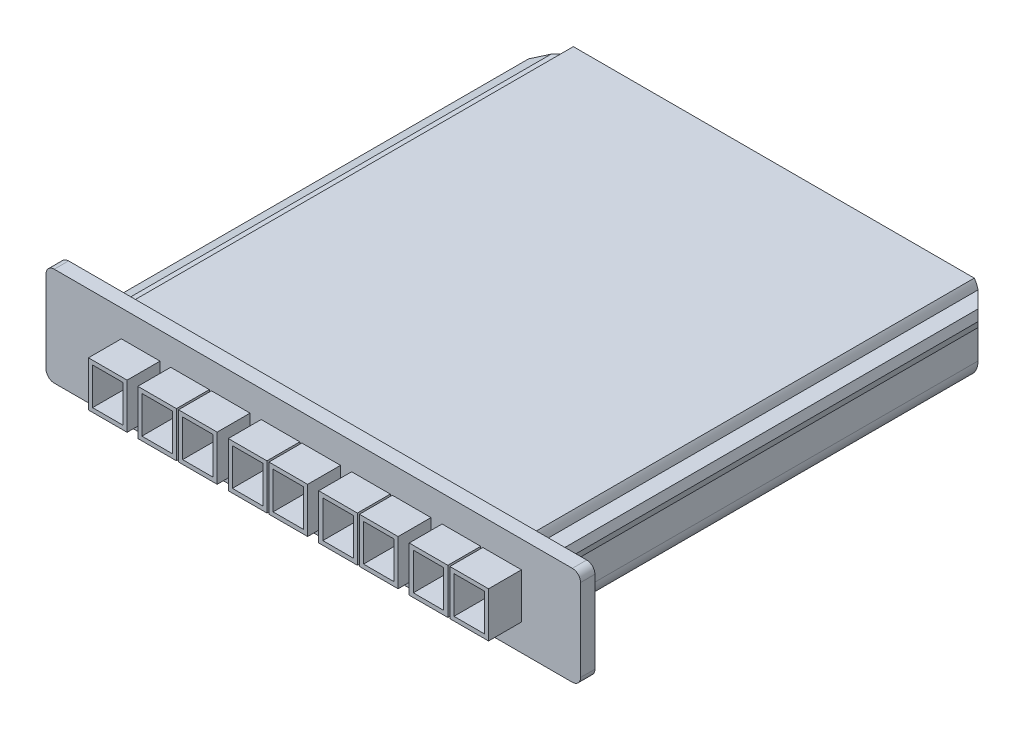
SolidWorks part; units mm, degrees
ref_plane "前视基准面" through (0, 0, 0) normal (0, 0, 1) x (1, 0, 0)
ref_plane "上视基准面" through (0, 0, 0) normal (0, 1, 0) x (1, 0, 0)
ref_plane "右视基准面" through (0, 0, 0) normal (1, 0, 0) x (0, 0, -1)
sketch "草图1" plane through (0, 0, 0) normal (0, 1, 0) x (1, 0, 0)
  line L0 (0, 117.5385) -> (0, -101.5385) construction
  line L1 (-65, 56) -> (65, 56)
  line L2 (-65, 56) -> (-65, -56)
  line L3 (-65, -56) -> (65, -56)
  line L4 (65, 56) -> (65, -56)
  line L5 (-199.7949, 0) -> (126.7692, 0) construction
  dimension "D1" = 112
  dimension "D2" = 130
extrude "凸台-拉伸1" add sketch "草图1" along normal blind 12 and the other way blind 12
sketch "草图2" plane through (0, 12, 0) normal (0, 1, 0) x (1, 0, 0)
  line L0 (0, 65.407) -> (0, -78.0498) construction
  line L1 (54.6587, 56) -> (54.6587, -52.5062)
  line L2 (-65, 56) -> (-54.6587, 56)
  line L3 (-65, 56) -> (-65, -52.5062)
  line L4 (-65, -52.5062) -> (-54.6587, -52.5062)
  line L5 (-54.6587, 56) -> (-54.6587, -52.5062)
  line L6 (65, -52.5062) -> (54.6587, -52.5062)
  line L7 (65, 56) -> (65, -52.5062)
  line L8 (65, 56) -> (54.6587, 56)
extrude "切除-拉伸1" cut sketch "草图2" against normal through all
sketch "草图3" plane through (-54.6587, 0, 0) normal (-1, 0, 0) x (0, 0, 1)
  line L0 (52.5062, -12) -> (52.5062, 12) construction
  line L1 (-56, 12) -> (52.5062, 12)
  line L2 (-56, 12) -> (-56, 7.9602)
  line L3 (-56, 7.9602) -> (52.5062, 7.9602)
  line L4 (52.5062, 12) -> (52.5062, 7.9602)
  line L6 (-56, -12) -> (52.5062, -12)
  line L7 (-56, -12) -> (-56, 4.0329)
  line L8 (-56, 4.0329) -> (52.5062, 4.0329)
  line L9 (52.5062, -12) -> (52.5062, 4.0329)
extrude "切除-拉伸2" cut sketch "草图3" against normal blind 5
mirror "镜向1" about plane through (0, 0, 0) normal (1, 0, 0) of "切除-拉伸2"
chamfer "倒角1" distance 5 angle 45 2 edges at (-54.6587, 5.9966, -56) (54.6587, 5.9966, -56)
fillet "圆角1" radius 5 4 edges at (49.6587, 12, -1.7469) (49.6587, -12, -1.7469) (-49.6587, -12, -1.7469) (-49.6587, 12, -1.7469)
chamfer "倒角2" distance 1 angle 70 4 edges at (54.6587, 7.9602, 0.7531) (54.6587, 4.0329, 0.7531) (-54.6587, 4.0329, 0.7531) (-54.6587, 7.9602, 0.7531) first distance on face at (52.1587, 7.9602, -0.4969) first distance on face at (52.1587, 4.0329, -0.4969) first distance on face at (-54.6587, 5.9966, 0.7531)
fillet "圆角2" radius 2 4 edges at (65, 12, 54.2531) (65, -12, 54.2531) (-65, -12, 54.2531) (-65, 12, 54.2531)
sketch "草图4" plane through (0, 0, 56) normal (0, 0, 1) x (1, 0, 0)
  line L0 (-76.0186, 0) -> (82.5881, 0) construction
  line L1 (-34.6736, 5.5) -> (-25.2736, 5.5)
  line L2 (-46.6736, 5.5) -> (-37.2736, 5.5)
  line L3 (-46.6736, 5.5) -> (-46.6736, -5.5)
  line L4 (-46.6736, -5.5) -> (-37.2736, -5.5)
  line L5 (-37.2736, 5.5) -> (-37.2736, -5.5)
  line L6 (-34.6736, 5.5) -> (-34.6736, -5.5)
  line L7 (-34.6736, -5.5) -> (-25.2736, -5.5)
  line L8 (-25.2736, 5.5) -> (-25.2736, -5.5)
  line L9 (-24.7736, 5.5) -> (-15.3736, 5.5)
  line L10 (-24.7736, 5.5) -> (-24.7736, -5.5)
  line L11 (-24.7736, -5.5) -> (-15.3736, -5.5)
  line L12 (-15.3736, 5.5) -> (-15.3736, -5.5)
  line L13 (-12.6736, 5.5) -> (-3.2736, 5.5)
  line L14 (-12.6736, 5.5) -> (-12.6736, -5.5)
  line L15 (-12.6736, -5.5) -> (-3.2736, -5.5)
  line L16 (-3.2736, 5.5) -> (-3.2736, -5.5)
  line L17 (-2.7736, 5.5) -> (6.6264, 5.5)
  line L18 (-2.7736, 5.5) -> (-2.7736, -5.5)
  line L19 (-2.7736, -5.5) -> (6.6264, -5.5)
  line L20 (6.6264, 5.5) -> (6.6264, -5.5)
  line L21 (9.3264, 5.5) -> (18.7264, 5.5)
  line L22 (9.3264, 5.5) -> (9.3264, -5.5)
  line L23 (9.3264, -5.5) -> (18.7264, -5.5)
  line L24 (18.7264, 5.5) -> (18.7264, -5.5)
  line L25 (19.2264, 5.5) -> (28.6264, 5.5)
  line L26 (19.2264, 5.5) -> (19.2264, -5.5)
  line L27 (19.2264, -5.5) -> (28.6264, -5.5)
  line L28 (28.6264, 5.5) -> (28.6264, -5.5)
  line L29 (31.3264, 5.5) -> (40.7264, 5.5)
  line L30 (31.3264, 5.5) -> (31.3264, -5.5)
  line L31 (31.3264, -5.5) -> (40.7264, -5.5)
  line L32 (40.7264, 5.5) -> (40.7264, -5.5)
  line L33 (41.2264, 5.5) -> (50.6264, 5.5)
  line L34 (41.2264, 5.5) -> (41.2264, -5.5)
  line L35 (41.2264, -5.5) -> (50.6264, -5.5)
  line L36 (50.6264, 5.5) -> (50.6264, -5.5)
  line L37 (-33.6736, 4.5) -> (-26.2736, 4.5)
  line L38 (-26.2736, 4.5) -> (-26.2736, -4.5)
  line L39 (-33.6736, -4.5) -> (-26.2736, -4.5)
  line L40 (-33.6736, 4.5) -> (-33.6736, -4.5)
  line L41 (-45.6736, 4.5) -> (-38.2736, 4.5)
  line L42 (-38.2736, 4.5) -> (-38.2736, -4.5)
  line L43 (-45.6736, -4.5) -> (-38.2736, -4.5)
  line L44 (-45.6736, 4.5) -> (-45.6736, -4.5)
  line L45 (-23.7736, 4.5) -> (-16.3736, 4.5)
  line L46 (-16.3736, 4.5) -> (-16.3736, -4.5)
  line L47 (-23.7736, -4.5) -> (-16.3736, -4.5)
  line L48 (-23.7736, 4.5) -> (-23.7736, -4.5)
  line L49 (-11.6736, 4.5) -> (-4.2736, 4.5)
  line L50 (-4.2736, 4.5) -> (-4.2736, -4.5)
  line L51 (-11.6736, -4.5) -> (-4.2736, -4.5)
  line L52 (-11.6736, 4.5) -> (-11.6736, -4.5)
  line L53 (-1.7736, 4.5) -> (5.6264, 4.5)
  line L54 (5.6264, 4.5) -> (5.6264, -4.5)
  line L55 (-1.7736, -4.5) -> (5.6264, -4.5)
  line L56 (-1.7736, 4.5) -> (-1.7736, -4.5)
  line L57 (10.3264, 4.5) -> (17.7264, 4.5)
  line L58 (17.7264, 4.5) -> (17.7264, -4.5)
  line L59 (10.3264, -4.5) -> (17.7264, -4.5)
  line L60 (10.3264, 4.5) -> (10.3264, -4.5)
  line L61 (20.2264, 4.5) -> (27.6264, 4.5)
  line L62 (27.6264, 4.5) -> (27.6264, -4.5)
  line L63 (20.2264, -4.5) -> (27.6264, -4.5)
  line L64 (20.2264, 4.5) -> (20.2264, -4.5)
  line L65 (32.3264, 4.5) -> (39.7264, 4.5)
  line L66 (39.7264, 4.5) -> (39.7264, -4.5)
  line L67 (32.3264, -4.5) -> (39.7264, -4.5)
  line L68 (32.3264, 4.5) -> (32.3264, -4.5)
  line L69 (42.2264, 4.5) -> (49.6264, 4.5)
  line L70 (49.6264, 4.5) -> (49.6264, -4.5)
  line L71 (42.2264, -4.5) -> (49.6264, -4.5)
  line L72 (42.2264, 4.5) -> (42.2264, -4.5)
  dimension "D1" = 9.4
  dimension "D2" = 11
  dimension "D6" = 1
  dimension "D3" = 2
  dimension "D4" = 2
  dimension "D5" = 4
extrude "凸台-拉伸2" add sketch "草图4" along normal blind 8
sketch "草图5" plane through (0, 12, 0) normal (0, 1, 0) x (1, 0, 0)
  line L1 (63, -52.5062) -> (-59.8054, -52.5062)
  line L2 (63, -52.5062) -> (63, 59.2527)
  line L3 (63, 59.2527) -> (-59.8054, 59.2527)
  line L4 (-59.8054, -52.5062) -> (-59.8054, 59.2527)
extrude "切除-拉伸3" cut sketch "草图5" against normal blind 2
mirror "镜向2" about plane through (0, 0, 0) normal (0, 1, 0) of "切除-拉伸3"
